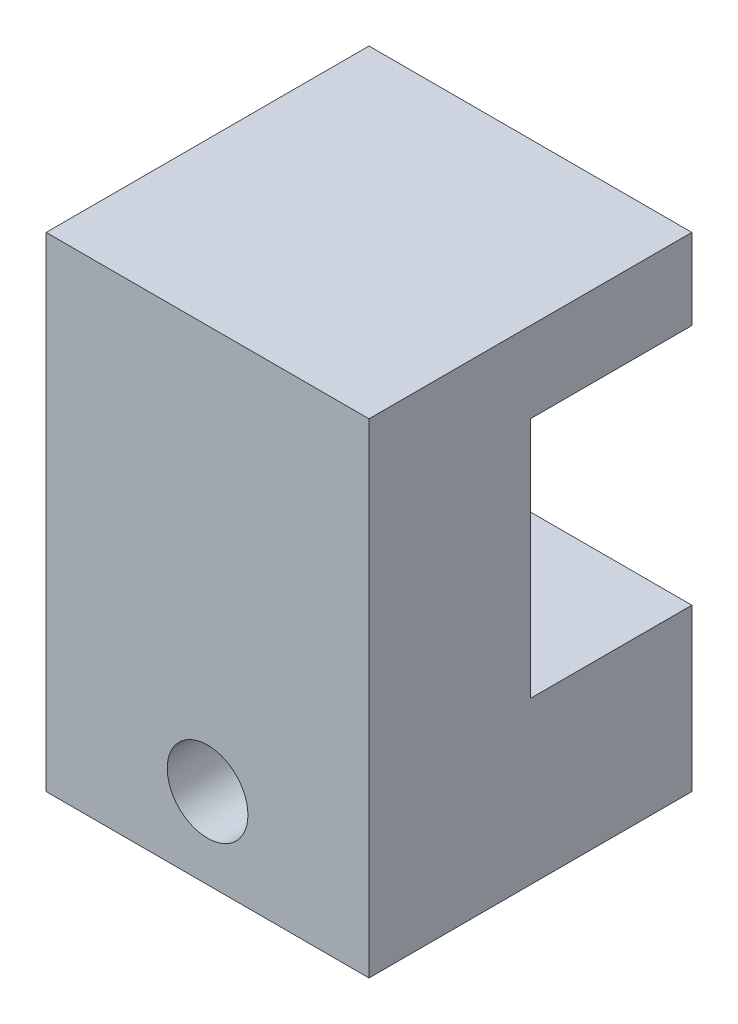
SolidWorks part; units mm, degrees
ref_plane "Front Plane" through (0, 0, 0) normal (0, 0, 1) x (1, 0, 0)
ref_plane "Top Plane" through (0, 0, 0) normal (0, 1, 0) x (1, 0, 0)
ref_plane "Right Plane" through (0, 0, 0) normal (1, 0, 0) x (0, 0, -1)
sketch "Sketch1" plane through (0, 0, 0) normal (0, 0, 1) x (1, 0, 0)
  line L1 (-12.7, -19.05) -> (12.7, -19.05)
  line L2 (-12.7, -19.05) -> (-12.7, 19.05)
  line L3 (-12.7, 19.05) -> (12.7, 19.05)
  line L4 (12.7, -19.05) -> (12.7, 19.05)
  line L5 (-12.7, -19.05) -> (12.7, 19.05) construction
  line L6 (-12.7, 19.05) -> (12.7, -19.05) construction
  point P0 (0, 0)
  dimension "D1" = 25.4
  dimension "D2" = 38.1
extrude "Boss-Extrude1" add sketch "Sketch1" along normal mid plane 25.4 contours L3 L4 L1 L2
sketch "Sketch2" plane through (0, 0, -12.7) normal (0, 0, -1) x (-1, 0, 0)
  line L0 (0, 55) -> (0, -55) construction
  line L1 (-12.7, -6.35) -> (12.7, -6.35)
  line L2 (-12.7, -6.35) -> (-12.7, 12.7)
  line L3 (-12.7, 12.7) -> (12.7, 12.7)
  line L4 (12.7, -6.35) -> (12.7, 12.7)
  line L5 (-12.7, -6.35) -> (12.7, 12.7) construction
  line L6 (-12.7, 12.7) -> (12.7, -6.35) construction
  line L7 (12.7, -19.05) -> (12.7, 19.05) construction
  line L8 (12.7, 19.05) -> (-12.7, 19.05) construction
  point P0 (0, 3.175)
  dimension "D1" = 15.875
  dimension "D2" = 19.05
extrude "Cut-Extrude1" cut sketch "Sketch2" against normal blind 12.7
sketch "Sketch3" plane through (0, 0, 12.7) normal (0, 0, 1) x (1, 0, 0)
  line L0 (0, -13.97) -> (0, 13.97) construction
  line L1 (-12.7, -19.05) -> (12.7, -19.05) construction
  circle A0 centre (0, -12.7) radius 3.175
  dimension "D1" = 6.35
  dimension "D2" = 6.35
extrude "Cut-Extrude2" cut sketch "Sketch3" against normal through all
